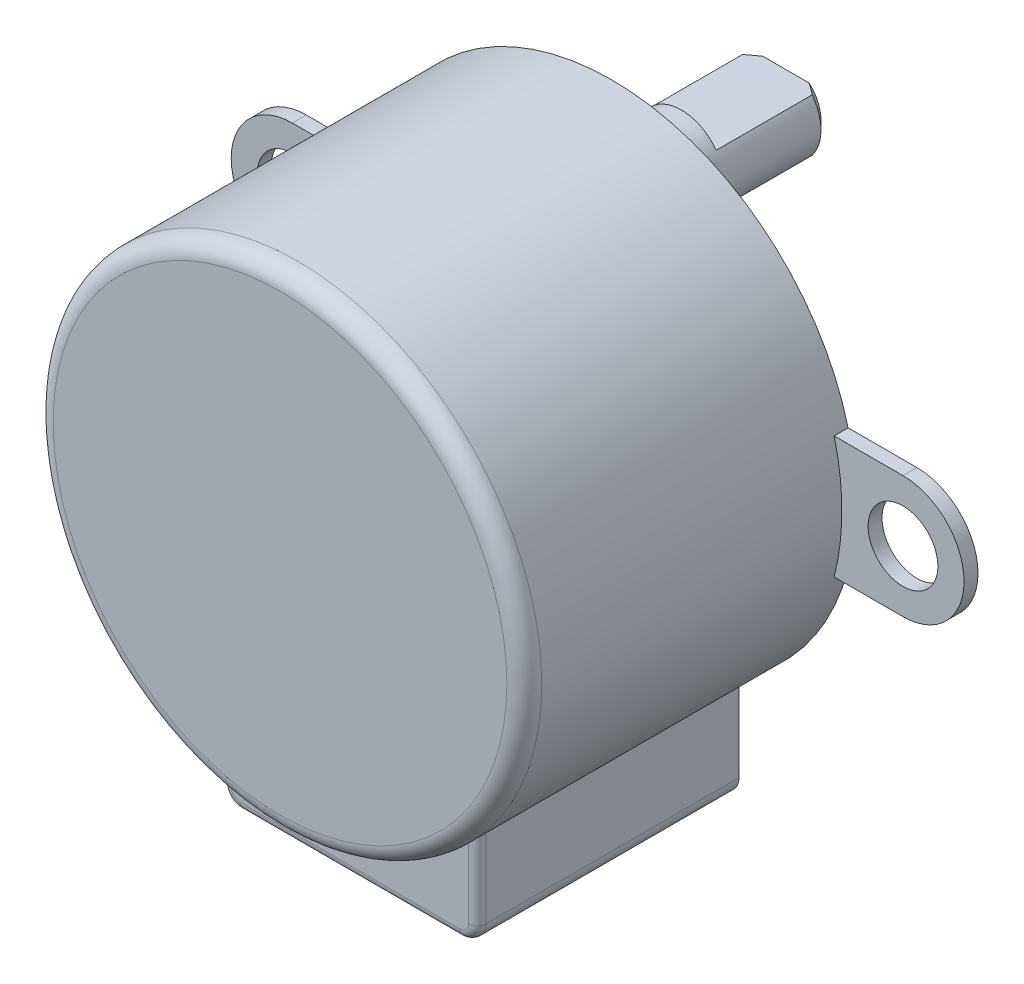
SolidWorks part; units mm, degrees
ref_plane "前视基准面" through (0, 0, 0) normal (0, 0, 1) x (1, 0, 0)
ref_plane "上视基准面" through (0, 0, 0) normal (0, 1, 0) x (1, 0, 0)
ref_plane "右视基准面" through (0, 0, 0) normal (1, 0, 0) x (0, 0, -1)
sketch "草图1" plane through (0, 0, 0) normal (0, 0, 1) x (1, 0, 0)
  circle A0 centre (0, 0) radius 14
  dimension "D1" = 28
extrude "凸台-拉伸1" add sketch "草图1" along normal blind 19
sketch "草图2" plane through (0, 0, 0) normal (0, 0, 1) x (1, 0, 0)
  line L0 (0, 20.4901) -> (0, -22.3048) construction
  line L1 (-24.8056, 0) -> (23.1683, 0) construction
  line L2 (-17.5, 3.5) -> (17.5, 3.5)
  line L3 (-17.5, -3.5) -> (17.5, -3.5)
  circle A0 centre (-17.5, 0) radius 2
  circle A1 centre (17.5, 0) radius 2
  arc A2 (-17.5, 3.5) -> (-17.5, -3.5) centre (-17.5, 0) ccw
  arc A3 (17.5, 3.5) -> (17.5, -3.5) centre (17.5, 0) cw
  dimension "D1" = 4
  dimension "D3" = 7
  dimension "D2" = 35
extrude "凸台-拉伸2" add sketch "草图2" along normal blind 0.8
sketch "草图3" plane through (0, 0, 0) normal (0, 0, -1) x (-1, 0, 0)
  circle A0 centre (0, 8) radius 4.5
  dimension "D1" = 9
  dimension "D2" = 8
extrude "凸台-拉伸3" add sketch "草图3" along normal blind 1.5
sketch "草图4" plane through (0, 0, -1.5) normal (0, 0, -1) x (-1, 0, 0)
  circle A0 centre (0, 8) radius 2.5
  dimension "D1" = 5
extrude "凸台-拉伸4" add sketch "草图4" along normal blind 8.5
sketch "草图5" plane through (0, 0, -10) normal (0, 0, -1) x (-1, 0, 0)
  line L1 (-6.1682, 6.5) -> (6.1682, 6.5)
  line L2 (-6.1682, 6.5) -> (-6.1682, 9.5)
  line L3 (-6.1682, 9.5) -> (6.1682, 9.5)
  line L4 (6.1682, 6.5) -> (6.1682, 9.5)
  line L5 (-6.1682, 6.5) -> (6.1682, 9.5) construction
  line L6 (-6.1682, 9.5) -> (6.1682, 6.5) construction
  point P0 (0, 8)
  dimension "D1" = 3
extrude "切除-拉伸1" cut sketch "草图5" against normal blind 6 flip side to cut
chamfer "倒角2" distance 0.5 angle 45 2 edges at (2.5, 8, -10) (-2.5, 8, -10)
sketch "草图6" plane through (0, 0, 0) normal (0, 0, -1) x (-1, 0, 0)
  line L0 (-24.1726, 0) -> (27.6734, 0) construction
  line L1 (0, 15.9206) -> (0, -16.4207) construction
  line L2 (-7.3, -9.4979) -> (7.3, -9.4979)
  line L3 (-7.3, -9.4979) -> (-7.3, -18)
  line L4 (-7.3, -18) -> (7.3, -18)
  line L5 (7.3, -9.4979) -> (7.3, -18)
  dimension "D1" = 18
  dimension "D2" = 14.6
extrude "凸台-拉伸5" add sketch "草图6" against normal blind 15
sketch "草图7" plane through (0, 0, 0) normal (0, 0, -1) x (-1, 0, 0)
  line L1 (-6.3, -11.3715) -> (-6.3, -17)
  line L2 (-6.3, -17) -> (6.3, -17)
  line L3 (-7.3, -11.9461) -> (-7.3, -18) construction
  line L4 (-7.3, -18) -> (7.3, -18) construction
  line L5 (6.3, -11.3715) -> (6.3, -17)
  arc A0 (6.3, -11.3715) -> (-6.3, -11.3715) centre (0, 0) ccw
  point P12 (0, -17)
  dimension "D1" = 26
  dimension "D2" = 1
  dimension "D3" = 1
split line "分割线1"
fillet "圆角1" radius 1 2 edges at (-7.3, -18, 7.5) (7.3, -18, 7.5)
fillet "圆角3" radius 1 1 edges at (14, 0, 19)
fillet "圆角4" radius 0.5 1 edges at (-4.5, 8, -1.5)
sketch "草图8" plane through (0, 0, 0) normal (0, 0, -1) x (-1, 0, 0)
  line L0 (-7.3, -11.9461) -> (-7.3, -10.7569)
  line L1 (7.3, -11.9461) -> (7.3, -10.7569)
  line L2 (6.3, -17) -> (6.3, -11.3715) construction
  line L3 (-6.3, -17) -> (6.3, -17) construction
  line L4 (-6.3, -11.3715) -> (-6.3, -17) construction
  line L5 (6.3, -17) -> (6.3, -11.3715)
  line L6 (-6.3, -17) -> (6.3, -17)
  line L7 (-6.3, -11.3715) -> (-6.3, -17)
  line L8 (7.3, -17) -> (7.3, -11.9461) construction
  line L9 (-6.3, -18) -> (6.3, -18) construction
  line L10 (-7.3, -11.9461) -> (-7.3, -17) construction
  line L11 (7.3, -17) -> (7.3, -11.9461)
  line L12 (-6.3, -18) -> (6.3, -18)
  line L13 (-7.3, -11.9461) -> (-7.3, -17)
  arc A0 (6.3, -11.3715) -> (-6.3, -11.3715) centre (0, 0) ccw construction
  arc A1 (6.3, -11.3715) -> (7.3, -10.7569) centre (0, 0) ccw
  arc A2 (-7.3, -10.7569) -> (-6.3, -11.3715) centre (0, 0) ccw
  arc A3 (6.3, -18) -> (7.3, -17) centre (6.3, -17) ccw construction
  arc A4 (-7.3, -17) -> (-6.3, -18) centre (-6.3, -17) ccw construction
  arc A5 (6.3, -18) -> (7.3, -17) centre (6.3, -17) ccw
  arc A6 (-7.3, -17) -> (-6.3, -18) centre (-6.3, -17) ccw
split line "分割线2"
fillet "圆角5" radius 0.5 8 edges at (7.3, -11.9461, 7.5) (-7.3, -11.9461, 7.5) (0, -14, 15) (7.3, -14.4731, 15) (7.0071, -17.7071, 15) (0, -18, 15) (-7.0071, -17.7071, 15) (-7.3, -14.4731, 15)
